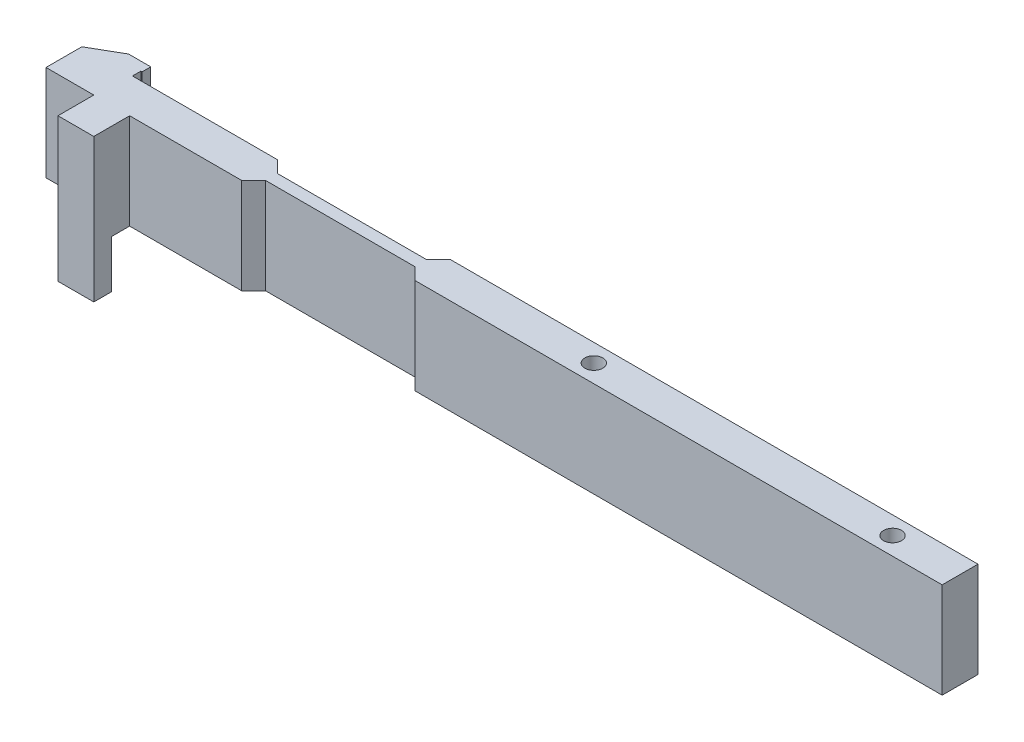
SolidWorks part; units mm, degrees
ref_plane "Спереди" through (0, 0, 0) normal (0, 0, 1) x (1, 0, 0)
ref_plane "Сверху" through (0, 0, 0) normal (0, 1, 0) x (1, 0, 0)
ref_plane "Справа" through (0, 0, 0) normal (1, 0, 0) x (0, 0, -1)
sketch "Эскиз1" plane through (0, 0, 0) normal (0, 1, 0) x (1, 0, 0)
  line L0 (0, 0) -> (-71.5259, 0)
  line L1 (-71.5259, 0) -> (-71.5259, 1.3965)
  line L2 (-71.5259, 1.3965) -> (-71.3259, 1.3965)
  line L3 (-71.3259, 1.3965) -> (-71.3259, 2.8586)
  line L4 (-71.3259, 2.8586) -> (-75.0357, 2.8586)
  line L5 (-75.0357, 2.8586) -> (-80, -0.0075)
  line L6 (-80, -0.0075) -> (-80, -6)
  line L7 (-80, -6) -> (70, -6)
  line L8 (70, -6) -> (70, 0)
  line L9 (70, 0) -> (0, 0)
  dimension "D1" = 150
  dimension "D2" = 30
  dimension "D3" = 0.2
  dimension "D4" = 6
  dimension "D5" = 70
extrude "Бобышка-Вытянуть1" add sketch "Эскиз1" along normal blind 16
sketch "Эскиз3" plane through (0, 16, 0) normal (0, 1, 0) x (1, 0, 0)
  line L0 (70, -3.0038) -> (-80, -3.0038) construction
  line L2 (-80, -0.0075) -> (-80, -6) construction
  line L3 (-47.2432, 0) -> (-45.2394, -2.0038)
  line L4 (70, 0) -> (-71.5259, 0) construction
  line L5 (-45.2394, -2.0038) -> (-20.2704, -2.0038)
  line L6 (-20.2704, -2.0038) -> (-18.2666, 0)
  line L7 (-47.2432, 0) -> (-18.2666, 0)
  line L8 (-47.2432, -6.0075) -> (-18.2666, -6.0075)
  line L9 (-20.2704, -4.0038) -> (-18.2666, -6.0075)
  line L10 (-45.2394, -4.0038) -> (-20.2704, -4.0038)
  line L11 (-47.2432, -6.0075) -> (-45.2394, -4.0038)
  circle A0 centre (8.6991, -3.0038) radius 1.5
  circle A1 centre (58.6991, -3.0038) radius 1.5
  point P18 (-69.785, -8.6152)
  dimension "D1" = 3
  dimension "D2" = 45
  dimension "D3" = 2
  dimension "D4" = 2
extrude "Вырез-Вытянуть1" cut sketch "Эскиз3" against normal through all
sketch "Эскиз4" plane through (0, 0, 0) normal (0, -1, 0) x (1, 0, 0)
  line L0 (-80, 6) -> (-47.2357, 6) construction
  line L1 (-80, 6) -> (-47.2357, 6) construction
  line L3 (-72, 12) -> (-66, 12)
  line L4 (-72, 12) -> (-72, 6)
  line L5 (-72, 6) -> (-66, 6)
  line L6 (-66, 12) -> (-66, 6)
  line L7 (-72, 12) -> (-66, 6) construction
  line L8 (-72, 6) -> (-66, 12) construction
  point P2 (-69, 9)
  dimension "D1" = 6
  dimension "D2" = 8
extrude "Бобышка-Вытянуть2" add sketch "Эскиз4" against normal up to surface (16 mm away) up to face at (58.6991, 16, 4.5038)
sketch "Эскиз5" plane through (0, 16, 0) normal (0, 1, 0) x (1, 0, 0)
  line L0 (-72, -12) -> (-72, -6)
  line L1 (-72, -6) -> (-69, -6)
  line L2 (-69, -6) -> (-66, -9)
  line L3 (-66, -12) -> (-66, -6) construction
  line L4 (-66, -9) -> (-66, -12)
  line L5 (-66, -12) -> (-72, -12)
  line L6 (-69, -12) -> (-69, -6) construction
extrude "Бобышка-Вытянуть3" [suppressed] add sketch "Эскиз5" along normal blind 8
extrude "Бобышка-Вытянуть4" add sketch "Эскиз5<2>" against normal blind 8 from surface starting at face at (58.6991, 0, 4.5038)
sketch "Эскиз5<2>" plane through (0, 16, 0) normal (0, 1, 0) x (1, 0, 0) same geometry as "Эскиз5"
